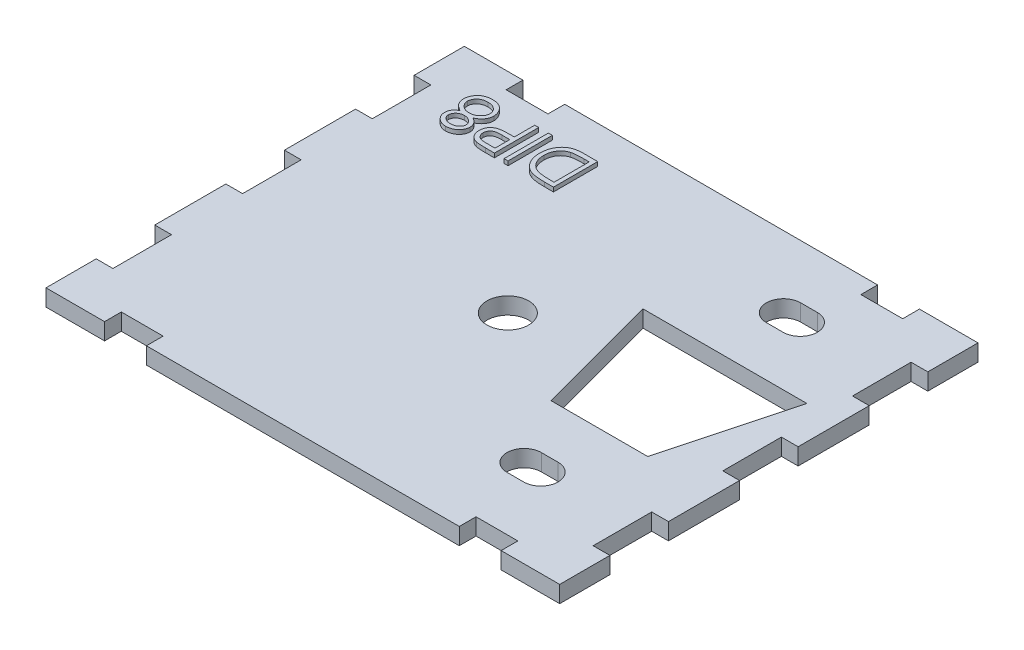
SolidWorks part; units mm, degrees
ref_plane "Front Plane" through (0, 0, 0) normal (0, 0, 1) x (1, 0, 0)
ref_plane "Top Plane" through (0, 0, 0) normal (0, 1, 0) x (1, 0, 0)
ref_plane "Right Plane" through (0, 0, 0) normal (1, 0, 0) x (0, 0, -1)
sketch "Sketch2" plane through (0, 0, 0) normal (0, 1, 0) x (1, 0, 0)
  line L1 (-50, 25) -> (50, 25)
  line L2 (-50, 25) -> (-50, -25)
  line L3 (-50, -25) -> (50, -25)
  line L4 (50, 25) -> (50, -25)
  line L5 (-50, 25) -> (50, -25) construction
  line L6 (-50, -25) -> (50, 25) construction
  point P0 (0, 0)
  dimension "D1" = 100
  dimension "D2" = 50
extrude "Boss-Extrude1" add sketch "Sketch2" along normal blind 2
sketch "Sketch12" plane through (0, 2, 0) normal (0, 1, 0) x (1, 0, 0)
  line L0 (-50, -25) -> (50, -25) construction
  line L1 (-40.2, -25) -> (-50, -25)
  line L2 (-40.2, -25) -> (-40.2, 25)
  line L3 (-40.2, 25) -> (-50, 25)
  line L4 (-50, -25) -> (-50, 25)
  line L5 (-50, -25) -> (50, -25) construction
  line L6 (41.2, -25) -> (50, -25)
  line L7 (41.2, -25) -> (41.2, 25)
  line L8 (41.2, 25) -> (50, 25)
  line L9 (50, -25) -> (50, 25)
extrude "Cut-Extrude8" cut sketch "Sketch12" against normal blind 6
sketch "Sketch13" plane through (0, 2, 0) normal (0, 1, 0) x (1, 0, 0)
  line L1 (-28.2, 19) -> (-30.2, 19)
  line L2 (-28.2, 19) -> (-28.2, 12)
  line L3 (-28.2, 12) -> (-30.2, 12)
  line L4 (-30.2, 19) -> (-30.2, 12)
  line L5 (-28.2, 3.5) -> (-30.2, 3.5)
  line L6 (-28.2, 3.5) -> (-28.2, -3.5)
  line L7 (-28.2, -3.5) -> (-30.2, -3.5)
  line L8 (-30.2, 3.5) -> (-30.2, -3.5)
  line L9 (-28.2, -12) -> (-30.2, -12)
  line L10 (-28.2, -12) -> (-28.2, -19)
  line L11 (-28.2, -19) -> (-30.2, -19)
  line L12 (-30.2, -12) -> (-30.2, -19)
  line L13 (29.2, 19) -> (31.2, 19)
  line L14 (29.2, 19) -> (29.2, 12)
  line L15 (29.2, 12) -> (31.2, 12)
  line L16 (31.2, 19) -> (31.2, 12)
  line L17 (29.2, 3.5) -> (31.2, 3.5)
  line L18 (29.2, 3.5) -> (29.2, -3.5)
  line L19 (29.2, -3.5) -> (31.2, -3.5)
  line L20 (31.2, 3.5) -> (31.2, -3.5)
  line L21 (29.2, -12) -> (31.2, -12)
  line L22 (29.2, -12) -> (29.2, -19)
  line L23 (29.2, -19) -> (31.2, -19)
  line L24 (31.2, -12) -> (31.2, -19)
  line L25 (-40.2, -25) -> (41.2, -25) construction
  line L26 (-23.2, 25) -> (-18.2, 25)
  line L27 (41.2, 25) -> (-40.2, 25) construction
  line L28 (-40.2, -25) -> (41.2, -25) construction
  line L29 (41.2, 25) -> (-40.2, 25) construction
  line L30 (-40.2, -25) -> (41.2, -25) construction
  line L31 (41.2, 25) -> (31.2, 25)
  line L32 (41.2, 25) -> (41.2, -25)
  line L33 (41.2, -25) -> (31.2, -25)
  line L34 (31.2, 25) -> (31.2, -25)
  line L35 (41.2, 25) -> (-40.2, 25) construction
  line L36 (-40.2, -25) -> (-30.2, -25)
  line L37 (-40.2, -25) -> (-40.2, 25)
  line L38 (-40.2, 25) -> (-30.2, 25)
  line L39 (-30.2, -25) -> (-30.2, 25)
  line L40 (-23.2, 25) -> (-23.2, 23)
  line L41 (-23.2, 23) -> (-18.2, 23)
  line L42 (-18.2, 25) -> (-18.2, 23)
  line L43 (-23.2, -25) -> (-18.2, -25)
  line L44 (-23.2, -25) -> (-23.2, -23)
  line L45 (-23.2, -23) -> (-18.2, -23)
  line L46 (-18.2, -25) -> (-18.2, -23)
  line L47 (24.2, -25) -> (19.2, -25)
  line L48 (24.2, -25) -> (24.2, -23)
  line L49 (24.2, -23) -> (19.2, -23)
  line L50 (19.2, -25) -> (19.2, -23)
  line L51 (24.2, 25) -> (19.2, 25)
  line L52 (24.2, 25) -> (24.2, 23)
  line L53 (24.2, 23) -> (19.2, 23)
  line L54 (19.2, 25) -> (19.2, 23)
  point P24 (29.2, 0)
  point P30 (30.2, 3.5)
  line M32 (41.2, -25) -> (41.2, 25)
  line M41 (41.2, 25) -> (-40.2, 25)
  line M42 (-40.2, 25) -> (-40.2, -25)
  line M47 (-40.2, -25) -> (41.2, -25)
  dimension "D1" = 2
  dimension "D2" = 2
  dimension "D3" = 2
  dimension "D4" = 2
  dimension "D5" = 2
  dimension "D6" = 2
  dimension "D7" = 57.4
  dimension "D8" = 57.4
  dimension "D9" = 57.4
  dimension "D10" = 7
  dimension "D11" = 7
  dimension "D12" = 7
  dimension "D13" = 7
  dimension "D14" = 7
  dimension "D15" = 7
  dimension "D16" = 5
  dimension "D17" = 2
  dimension "D18" = 5
  dimension "D19" = 6
  dimension "D20" = 8.5
  dimension "D21" = 8.5
  dimension "D22" = 6
  dimension "D23" = 6
  dimension "D24" = 8.5
  dimension "D25" = 8.5
  dimension "D26" = 6
  dimension "D27" = 5
  dimension "D28" = 5
  dimension "D29" = 2
  dimension "D30" = 2
  dimension "D31" = 5
  dimension "D32" = 5
  dimension "D33" = 5
  dimension "D34" = 5
  dimension "D35" = 2
extrude "Cut-Extrude10" cut sketch "Sketch13" against normal blind 6 contours L5 L8 L7 L6 | L39 L12 L8 L4 M47 M41 M42 | L1 L4 L3 L2 | L50 L48 L49 M47 | L24 L21 L22 L23 | L20 L17 L18 L19 | L16 L13 L14 L15 | L54 L53 L52 M41 | L9 L12 L11 L10 | L34 L16 L20 L24 M41 M47 M32 | L26 L42 L41 L40 | L45 L46 L43 L44 region at (-29.2, 2, -15.5) region at (-35.2, 2, 0) region at (-29.2, 2, 0) region at (-29.2, 2, 15.5) region at (21.7, 2, -24) region at (36.2, 2, 0) region at (21.7, 2, 24) region at (30.2, 2, -15.5) region at (30.2, 2, 0) region at (30.2, 2, 15.5)
sketch "Sketch15" plane through (0, 0, 0) normal (0, -1, 0) x (1, 0, 0)
  line L0 (24.2, 23) -> (19.2, 23) construction
  line L16 (20.7242, -7.5) -> (20.7242, -8.5)
  line L17 (20.7242, -7.5) -> (25.936, -7.5)
  line L18 (25.936, -7.5) -> (22.4527, 5.5)
  line L19 (22.4527, 5.5) -> (12.4527, 5.5)
  line L20 (12.4527, 5.5) -> (8.9693, -7.5)
  line L21 (8.9693, -7.5) -> (14.1811, -7.5)
  line L22 (14.1811, -7.5) -> (14.1811, -8.5)
  line L23 (14.1811, -8.5) -> (7.6661, -8.5)
  line L24 (7.6661, -8.5) -> (11.6853, 6.5)
  line L25 (11.6853, 6.5) -> (23.22, 6.5)
  line L26 (23.22, 6.5) -> (27.2392, -8.5)
  line L27 (27.2392, -8.5) -> (20.7242, -8.5)
  line L28 (20.7242, -8.5) -> (14.1811, -8.5)
  line L29 (14.1811, -7.5) -> (20.7242, -7.5)
  line L31 (29.2, 12) -> (29.2, 19) construction
  dimension "D4" = 16.5
  dimension "D18" = 11.5347
  dimension "D19" = 15.5291
  dimension "D20" = 15.5291
  dimension "D21" = 13.4586
  dimension "D22" = 13.4586
  dimension "D23" = 10
  dimension "D24" = 5.2118
  dimension "D25" = 5.2118
  dimension "D26" = 6.515
  dimension "D27" = 6.515
  dimension "D28" = 1
  dimension "D29" = 105
  dimension "D30" = 105
  dimension "D31" = 75
  dimension "D32" = 75
  dimension "D33" = 5.98
  dimension "D34" = 1
extrude "Cut-Extrude13" cut sketch "Sketch15" against normal blind 10 contours L21 L29 L17 L18 L19 L20 | L27 L26 L25 L24 L23 L22 L21 L20 L19 L18 L17 L16 | L29 L22 L28 L16 region at (23.3301, 0, -7.7466) region at (17.4527, 0, -1.5597) region at (17.4527, 0, -8)
sketch "Sketch16" plane through (0, 0, 0) normal (0, -1, 0) x (-1, 0, 0)
  circle A0 centre (0, 0) radius 2.5
  dimension "D1" = 5
extrude "Cut-Extrude14" cut sketch "Sketch16" against normal blind 10 contours A0
sketch "Sketch17" plane through (0, 0, 0) normal (0, -1, 0) x (-1, 0, 0)
  line L0 (-16.4527, 18.55) -> (-18.4527, 18.55)
  line L1 (-16.4527, 14.45) -> (-18.4527, 14.45)
  line L2 (-27.2392, 8.5) -> (-7.6661, 8.5) construction
  line L3 (-16.4527, -12.45) -> (-18.4527, -12.45)
  line L4 (-11.6853, -6.5) -> (-23.22, -6.5) construction
  line L5 (-18.4527, -16.55) -> (-16.4527, -16.55)
  circle A0 centre (-17.4527, -14.5) radius 2.05
  circle A1 centre (-17.4527, 16.5) radius 2.05
  circle A2 centre (-16.4527, 16.5) radius 2.05
  circle A3 centre (-18.4527, 16.5) radius 2.05
  circle A4 centre (-18.4527, -14.5) radius 2.05
  circle A5 centre (-16.4527, -14.5) radius 2.05
  dimension "D1" = 4.1
  dimension "D2" = 4.1
  dimension "D9" = 1
  dimension "D10" = 0
  dimension "D12" = 0
  dimension "D15" = 0
  dimension "D16" = 0
  dimension "D3" = 8
  dimension "D4" = 9.7866
  dimension "D5" = 9.7866
  dimension "D6" = 5.7673
  dimension "D7" = 5.7673
  dimension "D8" = 8
  dimension "D11" = 1
  dimension "D13" = 1
  dimension "D14" = 1
extrude "Cut-Extrude15" cut sketch "Sketch17" against normal blind 3.5 contours A4 A0 | A5 A4 A0 | A4 A5 | A0 A5 A4 | A5 A0 | A5 L3 A0 | A5 A0 A4 | A4 A0 L3 | A5 A0 L5 | A5 A4 A0 | A4 L5 A0 | A2 A3 | A1 A3 A2 | A3 A1 | A3 A2 A1 | A3 A1 A2 | A3 A2 A1 | A2 A1 | A2 A1 L1 | A3 L1 A1 | A3 A1 L0 | A2 L0 A1 region at (16.9527, 0, -18.5315) region at (15.3263, 0, -16.5) region at (17.9527, 0, -18.5315) region at (17.4527, 0, -18.454) region at (16.2506, 0, -16.5) region at (19.579, 0, -16.5) region at (18.6548, 0, -16.5) region at (16.9527, 0, -14.4685) region at (17.4527, 0, -16.5) region at (17.9527, 0, -14.4685) region at (17.4527, 0, -14.546) region at (16.9527, 0, 12.4685) region at (15.3263, 0, 14.5) region at (17.9527, 0, 12.4685) region at (17.4527, 0, 12.546) region at (16.2506, 0, 14.5) region at (19.579, 0, 14.5) region at (18.6548, 0, 14.5) region at (16.9527, 0, 16.5315) region at (17.4527, 0, 14.5) region at (17.9527, 0, 16.5315) region at (17.4527, 0, 16.454)
sketch "Sketch22" plane through (0, 2, 0) normal (0, 1, 0) x (1, 0, 0)
  line L0 (-24.5837, 20.5398) -> (4.8961, 20.5398) construction
  text T0 "DIP8" font "Century Gothic" height in points 20
extrude "Boss-Extrude4" add sketch "Sketch22" along normal blind 0.5
